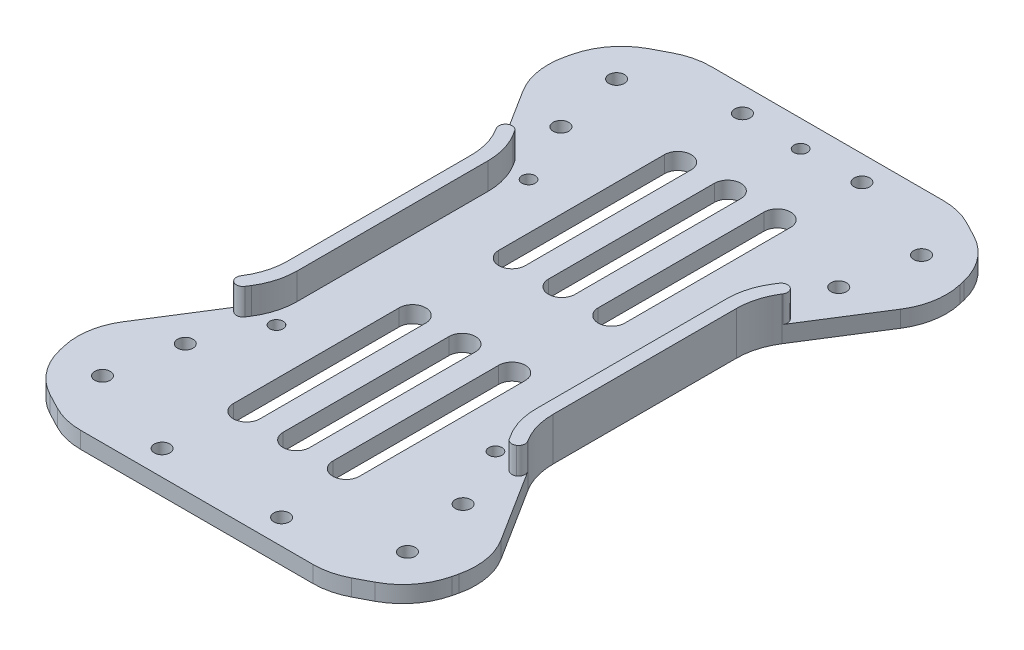
SolidWorks part; units mm, degrees
ref_plane "Plan de face" through (0, 0, 0) normal (0, 0, 1) x (1, 0, 0)
ref_plane "Plan de dessus" through (0, 0, 0) normal (0, 1, 0) x (1, 0, 0)
ref_plane "Plan de droite" through (0, 0, 0) normal (1, 0, 0) x (0, 0, -1)
sketch "Esquisse1" plane through (0, 0, 0) normal (0, 1, 0) x (1, 0, 0)
  line L0 (0, 95) -> (0, -95) construction
  line L1 (40, -95) -> (-40, -95)
  line L2 (-40, -95) -> (-61.4148, -67.316)
  line L3 (-61.4148, -67.316) -> (-40, -33.4103)
  line L4 (-40, -33.4103) -> (-40, 33.4103)
  line L5 (-40, 33.4103) -> (-61.4148, 67.316)
  line L6 (-61.4148, 67.316) -> (-40, 95)
  line L7 (-40, 95) -> (40, 95)
  line L8 (-40, -95) -> (-40, 95) construction
  line L9 (-90.2912, 0) -> (0, 0) construction
  line L10 (50.7074, 81.158) -> (185.1727, 185.1727) construction
  line L11 (-50.7074, 81.158) -> (-185.1727, 185.1727) construction
  line L12 (40, -95) -> (40, 95) construction
  line L13 (61.4148, 67.316) -> (40, 95)
  line L14 (40, 33.4103) -> (61.4148, 67.316)
  line L15 (40, -33.4103) -> (40, 33.4103)
  line L16 (61.4148, -67.316) -> (40, -33.4103)
  line L17 (40, -95) -> (61.4148, -67.316)
  line L18 (50.7074, -81.158) -> (185.1727, -185.1727) construction
  line L19 (-50.7074, -81.158) -> (-185.1727, -185.1727) construction
  line L20 (-185.1727, 185.1727) -> (185.1727, 185.1727) construction
  line L21 (-185.1727, 185.1727) -> (-185.1727, -185.1727) construction
  line L22 (-50.7074, 81.158) -> (-11.4576, 50.7965) construction
  circle A0 centre (18.0097, 87.4716) radius 2.35
  circle A1 centre (45.9633, 77.4882) radius 2.35
  circle A2 centre (41.8719, 56.6236) radius 2.35
  circle A3 centre (-41.8719, 56.6236) radius 2.35
  circle A4 centre (-45.9633, 77.4882) radius 2.35
  circle A5 centre (-18.0097, 87.4716) radius 2.35
  circle A6 centre (41.8719, -56.6236) radius 2.35
  circle A7 centre (45.9633, -77.4882) radius 2.35
  circle A8 centre (18.0097, -87.4716) radius 2.35
  circle A9 centre (-18.0097, -87.4716) radius 2.35
  circle A10 centre (-45.9633, -77.4882) radius 2.35
  circle A11 centre (-41.8719, -56.6236) radius 2.35
  dimension "D10" = 4.7
  dimension "D11" = 4.7
  dimension "D12" = 4.7
  dimension "D1" = 40
  dimension "D2" = 190
  dimension "D3" = 110
  dimension "D4" = 35
  dimension "D5" = 170
  dimension "D6" = 170
  dimension "D7" = 170
  dimension "D8" = 170
  dimension "D9" = 127.724
extrude "Boss.-Extru.1" add sketch "Esquisse1" along normal blind 5
sketch "Esquisse3" plane through (0, 5, 0) normal (0, 1, 0) x (1, 0, 0)
  line L0 (40, -33.4103) -> (40, 33.4103)
  line L1 (40, 33.4103) -> (44.272, 40.1741)
  line L2 (40, 33.4103) -> (61.4148, 67.316) construction
  line L3 (44.272, 40.1741) -> (40.8901, 42.3102)
  line L4 (40.8901, 42.3102) -> (36, 34.5677)
  line L5 (36, 34.5677) -> (36, -34.5677)
  line L6 (40, -33.4103) -> (44.272, -40.1741)
  line L8 (44.272, -40.1741) -> (40.8901, -42.3102)
  line L9 (40.8901, -42.3102) -> (36, -34.5677)
  line L10 (61.4148, -67.316) -> (40, -33.4103) construction
  line L11 (0, -68.9117) -> (0, 72.8975) construction
  line L12 (-40.8901, -42.3102) -> (-36, -34.5677)
  line L13 (-44.272, -40.1741) -> (-40.8901, -42.3102)
  line L14 (-40, -33.4103) -> (-44.272, -40.1741)
  line L15 (-36, 34.5677) -> (-36, -34.5677)
  line L16 (-40.8901, 42.3102) -> (-36, 34.5677)
  line L17 (-44.272, 40.1741) -> (-40.8901, 42.3102)
  line L18 (-40, 33.4103) -> (-44.272, 40.1741)
  line L19 (-40, -33.4103) -> (-40, 33.4103)
  dimension "D1" = 4
  dimension "D2" = 4
  dimension "D3" = 4
  dimension "D4" = 8
  dimension "D6" = 8
extrude "Boss.-Extru.2" add sketch "Esquisse3" along normal blind 8
fillet "Congé3" radius 2 8 edges at (-40.8901, 9, -42.3102) (-44.272, 9, -40.1741) (-44.272, 9, 40.1741) (-40.8901, 9, 42.3102) (40.8901, 9, 42.3102) (40.8901, 9, -42.3102)
fillet "Congé4" radius 20 4 edges at (40, 6.5, -33.4103) (-40, 6.5, -33.4103) (-40, 6.5, 33.4103) (40, 6.5, 33.4103)
sketch "Esquisse4" plane through (0, 0, 0) normal (0, -1, 0) x (-1, 0, 0)
  line L0 (0, -61.7793) -> (0, 73.5268) construction
  circle A0 centre (33, -38) radius 2
  circle A1 centre (33, 38) radius 2
  circle A2 centre (-33, -38) radius 2
  circle A3 centre (-33, 38) radius 2
  dimension "D1" = 4
  dimension "D2" = 4
extrude "Enlèv. mat.-Extru.1" cut sketch "Esquisse4" against normal through all
fillet "Congé5" radius 20 4 edges at (36, 9, 34.5677) (36, 9, -34.5677) (-36, 9, 34.5677) (-36, 9, -34.5677)
sketch "Esquisse5" plane through (0, 5, 0) normal (0, 1, 0) x (1, 0, 0)
  line L0 (-15, -65) -> (-15, -15) construction
  line L1 (-19, -65) -> (-19, -15)
  line L2 (-11, -65) -> (-11, -15)
  line L3 (-31.8772, 0) -> (31.8489, 0) construction
  line L4 (0, -72.9597) -> (0, 72.252) construction
  line L5 (15, -65) -> (15, -15) construction
  line L6 (19, -65) -> (19, -15)
  line L7 (11, -65) -> (11, -15)
  line L8 (15, 65) -> (15, 15) construction
  line L9 (19, 65) -> (19, 15)
  line L10 (11, 65) -> (11, 15)
  line L11 (-15, 65) -> (-15, 15) construction
  line L12 (-19, 65) -> (-19, 15)
  line L13 (-11, 65) -> (-11, 15)
  line L14 (0, -65) -> (0, -15) construction
  line L15 (-4, -65) -> (-4, -15)
  line L16 (4, -65) -> (4, -15)
  line L17 (0, 65) -> (0, 15) construction
  line L18 (-4, 65) -> (-4, 15)
  line L19 (4, 65) -> (4, 15)
  line L20 (15, -15) -> (-15, -15) construction
  line L21 (19, -65) -> (-19, -65) construction
  arc A0 (-19, -65) -> (-11, -65) centre (-15, -65) ccw
  arc A1 (-11, -15) -> (-19, -15) centre (-15, -15) ccw
  arc A2 (19, -65) -> (11, -65) centre (15, -65) cw
  arc A3 (11, -15) -> (19, -15) centre (15, -15) cw
  arc A4 (19, 65) -> (11, 65) centre (15, 65) ccw
  arc A5 (11, 15) -> (19, 15) centre (15, 15) ccw
  arc A6 (-19, 65) -> (-11, 65) centre (-15, 65) cw
  arc A7 (-11, 15) -> (-19, 15) centre (-15, 15) cw
  arc A8 (-4, -65) -> (4, -65) centre (0, -65) ccw
  arc A9 (4, -15) -> (-4, -15) centre (0, -15) ccw
  arc A10 (-4, 65) -> (4, 65) centre (0, 65) cw
  arc A11 (4, 15) -> (-4, 15) centre (0, 15) cw
  point P2 (-15, -40)
  point P14 (15, -40)
  point P21 (15, 40)
  point P28 (-15, 40)
  point P35 (0, -40)
  point P42 (0, 40)
  dimension "D1" = 15
  dimension "D2" = 40
  dimension "D3" = 50
  dimension "D4" = 8
  dimension "D6" = 8
extrude "Enlèv. mat.-Extru.2" cut sketch "Esquisse5" against normal through all
sketch "Esquisse6" plane through (0, 5, 0) normal (0, 1, 0) x (1, 0, 0)
  line L0 (0, -113.2261) -> (0, 120.8582) construction
  line L1 (-61.4148, 67.316) -> (-57.0352, 86.0528)
  line L2 (-57.0352, 86.0528) -> (-40, 95)
  line L3 (-50.7074, 81.158) -> (-74.983, 99.9362) construction
  line L4 (-40, 95) -> (-61.4148, 67.316) construction
  line L5 (-100.5493, 0) -> (112.1425, 0) construction
  line L6 (57.0352, 86.0528) -> (40, 95)
  line L7 (61.4148, 67.316) -> (57.0352, 86.0528)
  line L8 (61.4148, -67.316) -> (57.0352, -86.0528)
  line L9 (57.0352, -86.0528) -> (40, -95)
  line L10 (-57.0352, -86.0528) -> (-40, -95)
  line L11 (-61.4148, -67.316) -> (-57.0352, -86.0528)
  line L12 (-61.4148, 67.316) -> (-40, 95)
  line L13 (40, 95) -> (61.4148, 67.316)
  line L14 (-61.4148, -67.316) -> (-40, -95)
  line L15 (40, -95) -> (61.4148, -67.316)
  dimension "D1" = 8
extrude "Boss.-Extru.3" add sketch "Esquisse6" against normal blind 5
fillet "Congé6" radius 20 4 edges at (57.0352, 2.5, 86.0528) (-57.0352, 2.5, 86.0528) (57.0352, 2.5, -86.0528) (-57.0352, 2.5, -86.0528)
fillet "Congé7" radius 20 8 edges at (-40, 2.5, 95) (-61.4148, 2.5, 67.316) (40, 2.5, 95) (61.4148, 2.5, 67.316) (61.4148, 2.5, -67.316) (40, 2.5, -95) (-61.4148, 2.5, -67.316) (-40, 2.5, -95)
sketch "Esquisse7" plane through (0, 0, 0) normal (0, -1, 0) x (-1, 0, 0)
  circle A0 centre (0, 87) radius 2
  dimension "D1" = 4
extrude "Enlèv. mat.-Extru.3" cut sketch "Esquisse7" against normal blind 10
